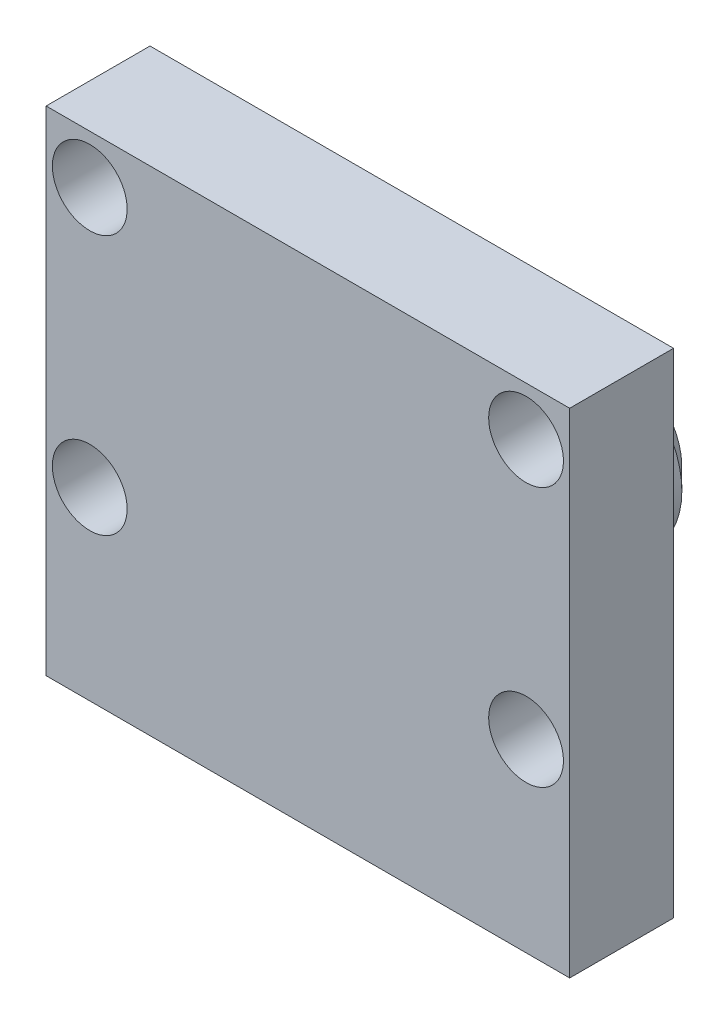
SolidWorks part; units mm, degrees
ref_plane "Front Plane" through (0, 0, 0) normal (0, 0, 1) x (1, 0, 0)
ref_plane "Top Plane" through (0, 0, 0) normal (0, 1, 0) x (1, 0, 0)
ref_plane "Right Plane" through (0, 0, 0) normal (1, 0, 0) x (0, 0, -1)
sketch "Sketch1" plane through (0, 0, 0) normal (0, 0, 1) x (1, 0, 0)
  line L0 (12.7, 36.9) -> (12.7, 40.9) construction
  line L1 (12.7, 49.4) -> (12.7, 54) construction
  line L2 (12.7, 54) -> (8.5, 54) construction
  line L3 (-12.7, 40.9) -> (-12.7, 36.9) construction
  line L4 (-12.7, 54) -> (-12.7, 49.4) construction
  line L5 (-8.5, 54) -> (-12.7, 54) construction
  line L6 (-6, 33) -> (6, 33) construction
  line L7 (6, 33) -> (6, 45) construction
  line L8 (6, 45) -> (-6, 45) construction
  line L9 (-6, 45) -> (-6, 33) construction
  line L10 (12.7, 36.9) -> (12.7, 40.9)
  line L11 (12.7, 49.4) -> (12.7, 54)
  line L12 (12.7, 54) -> (8.5, 54)
  line L13 (-12.7, 40.9) -> (-12.7, 36.9)
  line L14 (-12.7, 54) -> (-12.7, 49.4)
  line L15 (-8.5, 54) -> (-12.7, 54)
  line L16 (-6, 33) -> (6, 33)
  line L17 (6, 33) -> (6, 45)
  line L18 (6, 45) -> (-6, 45)
  line L19 (-6, 45) -> (-6, 33)
  circle A0 centre (10.5, 51.4) radius 1.1 construction
  circle A1 centre (10.5, 38.9) radius 1.1 construction
  circle A2 centre (-10.5, 38.9) radius 1.1 construction
  circle A3 centre (-10.5, 51.4) radius 1.1 construction
  circle A4 centre (10.5, 51.4) radius 1.1
  circle A5 centre (10.5, 38.9) radius 1.1
  circle A6 centre (-10.5, 38.9) radius 1.1
  circle A7 centre (-10.5, 51.4) radius 1.1
sketch "Sketch2" plane through (0, 0, 0) normal (0, 0, 1) x (1, 0, 0)
  line L0 (-12.7, 54) -> (-12.7, 49.4) construction
  line L1 (-12.6, 30) -> (12.6, 30)
  line L2 (-12.6, 30) -> (-12.6, 53.75)
  line L3 (-12.6, 53.75) -> (12.6, 53.75)
  line L4 (12.6, 30) -> (12.6, 53.75)
  line L5 (-12.6, 30) -> (12.6, 53.75) construction
  line L6 (-12.6, 53.75) -> (12.6, 30) construction
  line L7 (-8.5, 54) -> (-12.7, 54) construction
  line L8 (12.7, 49.4) -> (12.7, 54) construction
  line L9 (-6, 33) -> (6, 33) construction
  point P0 (0, 41.875)
  dimension "D1" = 0.1
  dimension "D2" = 0.25
  dimension "D3" = 0.1
  dimension "D4" = 3
extrude "Boss-Extrude1" add sketch "Sketch2" along normal blind 5
sketch "Sketch3" plane through (0, 0, 0) normal (0, 0, -1) x (-1, 0, 0)
  circle A0 centre (-10.5, 51.4) radius 1.8
  circle A1 centre (10.5, 51.4) radius 1.8
  circle A2 centre (10.5, 38.9) radius 1.8
  circle A3 centre (-10.5, 38.9) radius 1.8
  dimension "D1" = 3.6
extrude "Cut-Extrude1" cut sketch "Sketch3" against normal through all
sketch "Sketch4" plane through (0, 0, 0) normal (0, 0, -1) x (-1, 0, 0)
  line L0 (-6, 45) -> (6, 33) construction
  line L1 (6, 45) -> (6, 33) construction
  line L2 (-5.6, 33.4) -> (5.6, 33.4)
  line L3 (-5.6, 33.4) -> (-5.6, 44.6)
  line L4 (-5.6, 44.6) -> (5.6, 44.6)
  line L5 (5.6, 33.4) -> (5.6, 44.6)
  line L6 (-5.6, 33.4) -> (5.6, 44.6) construction
  line L7 (-5.6, 44.6) -> (5.6, 33.4) construction
  line L8 (-6, 45) -> (6, 45) construction
  point P4 (0, 39)
  dimension "D1" = 0.4
  dimension "D2" = 0.4
extrude "Boss-Extrude2" add sketch "Sketch4" along normal blind 6
sketch "Sketch5" plane through (0, 0, -6) normal (0, 0, -1) x (-1, 0, 0)
  line L0 (-5.6, 33.4) -> (5.6, 44.6) construction
  circle A0 centre (0, 39) radius 4
  dimension "D1" = 8
extrude "Boss-Extrude3" add sketch "Sketch5" along normal blind 4
sketch "Sketch6" plane through (0, 0, -10) normal (0, 0, -1) x (-1, 0, 0)
  circle A0 centre (0, 39) radius 2.5
  dimension "D1" = 5
extrude "Cut-Extrude2" cut sketch "Sketch6" against normal blind 1
extrude "Boss-Extrude4" add sketch "Sketch6<2>" against normal up to surface (1 mm away) separate body up to face at (-2.5, 39, -9)
sketch "Sketch6<2>" plane through (0, 0, -10) normal (0, 0, -1) x (-1, 0, 0) same geometry as "Sketch6"
chamfer "Chamfer1" distance 1 angle 45 5 edges at (-4, 39, -10) (0, 44.6, -6) (-5.6, 39, -6) (5.6, 39, -6) (0, 33.4, -6)
